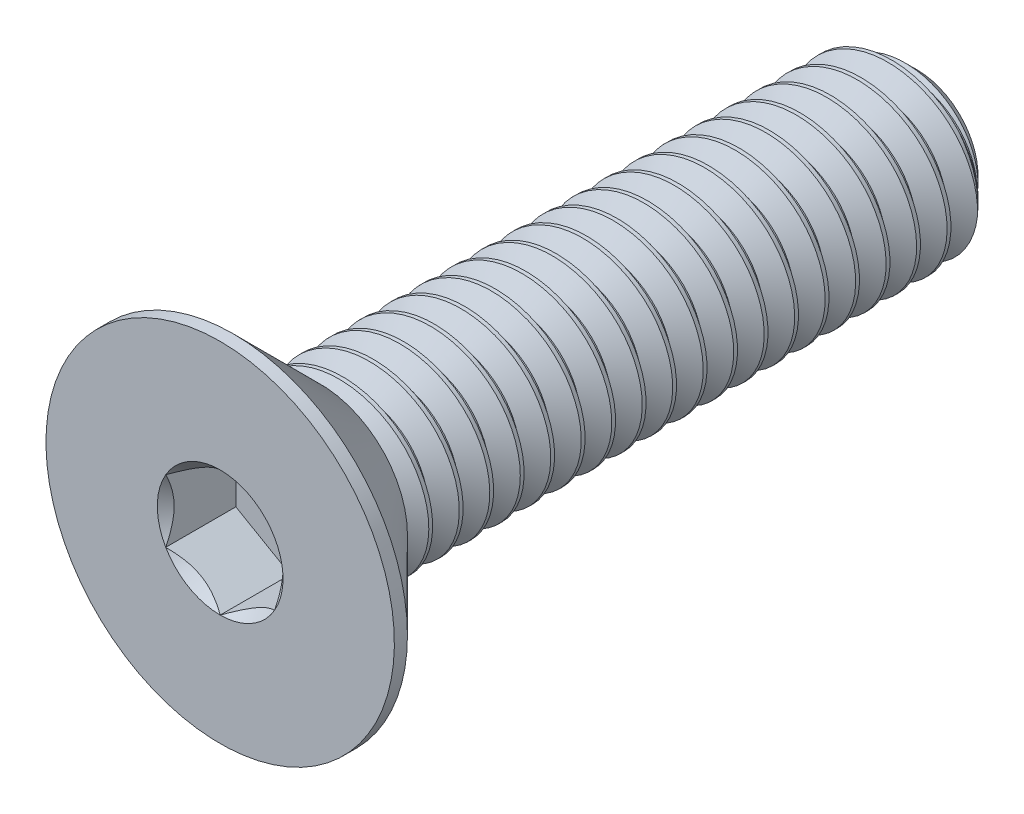
SolidWorks part; units mm, degrees
material "Alloy Steel"
ref_plane "Front" through (0, 0, 0) normal (0, 0, 1) x (1, 0, 0)
ref_plane "Top" through (0, 0, 0) normal (0, 1, 0) x (1, 0, 0)
ref_plane "Right" through (0, 0, 0) normal (1, 0, 0) x (0, 0, -1)
sketch "Sketch1" plane through (0, 0, 0) normal (1, 0, 0) x (0, 0, -1)
  line L0 (-8, 4) -> (-7.7, 4) construction
  line L1 (-7.7, 4) -> (-5.7, 2) construction
  line L2 (-8, 2) -> (8, 2) construction
  line L3 (8, 2) -> (8, 0) construction
  line L4 (8, 0) -> (-8, 0) construction
  line L5 (-8, 0) -> (-8, 4) construction
  line L6 (-8, 4) -> (-8, -4) construction
  line L7 (8, 2) -> (8, -2) construction
  line L8 (-8, -4) -> (-7.7, -4) construction
  line L9 (-7.7, -4) -> (-5.7, -2) construction
  line L11 (-8, 2) -> (-8, 0) construction
  line L12 (-5.7, 2) -> (-5.7, 0) construction
  line L13 (7.9563, 2.0758) -> (8.3063, 1.4696) construction
  line L14 (8.3063, 1.4696) -> (8.6563, 2.0758) construction
  line L15 (8.6563, 2.0758) -> (7.9563, 2.0758) construction
  line L16 (8.3063, 2.0758) -> (8.3063, 2) construction
  line L17 (8.3063, 2) -> (8.3063, 1.5453) construction
  line L18 (8.3063, 1.5453) -> (8.3063, 1.4696) construction
  line L19 (8.3063, 2.0379) -> (8.6344, 2.0379) construction
  line L20 (8.3063, 2.0379) -> (7.9781, 2.0379) construction
  line L21 (8, 2) -> (8.6125, 2) construction
  line L22 (8.2625, 1.5453) -> (8.35, 1.5453) construction
  line L23 (8, -2) -> (-5.7, -2) construction
  point P10 (6.25, -2)
  point P24 (-5.7, 2)
  point P30 (0, 0)
  dimension "Head Diameter" = 8
  dimension "Head Height" = 2.3
  dimension "Length" = 16
  dimension "Countersink Angle" = 90
  dimension "Thread Pitch" = 0.7
  dimension "D2" = 0.0875
  dimension "Thread Size" = 4
  dimension "D1" = 1.75
sketch "Sketch2" plane through (0, 0, 0) normal (0, 0, 1) x (1, 0, 0)
  line L1 (0, 1.4434) -> (-1.25, 0.7217) construction
  line L2 (-1.25, 0.7217) -> (-1.25, -0.7217) construction
  line L3 (-1.25, -0.7217) -> (0, -1.4434) construction
  line L4 (0, -1.4434) -> (1.25, -0.7217) construction
  line L5 (1.25, -0.7217) -> (1.25, 0.7217) construction
  line L6 (1.25, 0.7217) -> (0, 1.4434) construction
  circle A0 centre (0, 0) radius 1.25 construction
  dimension "Drive Size" = 2.5
sketch "Sketch3" plane through (0, 0, 0) normal (1, 0, 0) x (0, 0, -1)
  line L0 (-8, 2) -> (8, 2)
  line L1 (8, 2) -> (8, 0)
  line L2 (8, 0) -> (-8, 0)
  line L3 (-8, 0) -> (-8, 2)
revolve "Revolve1" add sketch "Sketch3" angle 360 about L4
chamfer "Chamfer1" distance 0.6 angle 45 1 edges at (0, 2, -8)
sketch "Sketch6" plane through (0, 0, 0) normal (1, 0, 0) x (0, 0, -1)
  line L0 (-8, 4) -> (-7.7, 4)
  line L1 (-7.7, 4) -> (-5.7, 2)
  line L2 (-5.7, 2) -> (-5.7, 0)
  line L3 (-5.7, 0) -> (-8, 0)
  line L4 (-8, 0) -> (-8, 4)
revolve "Revolve2" add sketch "Sketch6" angle 360 about L4
sketch "Sketch8" plane through (0, 0, 8) normal (0, 0, 1) x (1, 0, 0)
  line L0 (0, 1.4434) -> (-1.25, 0.7217) construction
  line L1 (1.25, 0.7217) -> (0, 1.4434) construction
  line L2 (1.25, -0.7217) -> (1.25, 0.7217) construction
  line L3 (0, -1.4434) -> (1.25, -0.7217) construction
  line L4 (-1.25, 0.7217) -> (-1.25, -0.7217) construction
  line L5 (-1.25, -0.7217) -> (0, -1.4434) construction
  line L6 (0, 1.4434) -> (-1.25, 0.7217)
  line L7 (1.25, 0.7217) -> (0, 1.4434)
  line L8 (1.25, -0.7217) -> (1.25, 0.7217)
  line L9 (0, -1.4434) -> (1.25, -0.7217)
  line L10 (-1.25, 0.7217) -> (-1.25, -0.7217)
  line L11 (-1.25, -0.7217) -> (0, -1.4434)
extrude "Cut-Extrude1" cut sketch "Sketch8" against normal blind 1.61
sketch "Sketch9" plane through (0, 0, 8) normal (0, 0, 1) x (1, 0, 0)
  circle A0 centre (0, 0) radius 1.4434
extrude "Cut-Extrude2" cut sketch "Sketch9" against normal up to next (1.61 mm away) draft 45
ref_plane "Plane1" through (0, 0, 5.7) normal (0, 0, 1) x (1, 0, 0)
split "Split1" trim tools "Plane1" bodies to split 124 resulting bodies 126 127
sketch "Sketch4" plane through (0, 0, -8) normal (0, 0, -1) x (-1, 0, 0)
  circle A0 centre (0, 0) radius 2 construction
  circle A1 centre (0, 0) radius 2
curve "Helix/Spiral1" pitch 0.7 height 16 radius 2 centre (0, 0, -8) axis (0, 0, 1) start towards (0, 1, 0)
sketch "Sketch10" plane through (0, 0, 0) normal (1, 0, 0) x (0, 0, -1)
  line L0 (7.9781, 2.0379) -> (8.6344, 2.0379)
  line L1 (8.6344, 2.0379) -> (8.35, 1.5453)
  line L2 (8.35, 1.5453) -> (8.2625, 1.5453)
  line L3 (8.2625, 1.5453) -> (7.9781, 2.0379)
sweep "Cut-Sweep1" cut profiles "Sketch10" path "Helix/Spiral1" align with end faces yes
combine bodies "Combine1" operation type add bodies to combine 130 126
equation "\"D2@Sketch1\" = \"Thread Pitch@Sketch1\" / 8"
equation "\"D4@Helix/Spiral1\"=\"Thread Pitch@Sketch1\""
equation "\"D1@Chamfer1\"=\"Thread Size@Sketch1\"*.15"
equation "\"D1@Cut-Extrude1\"=\"Head Height@Sketch1\"*.7"
equation "\"D1@Sketch1\"=\"Thread Pitch@Sketch1\"*2.5"
equation "\"D3@Helix/Spiral1\"=\"Length@Sketch1\""
